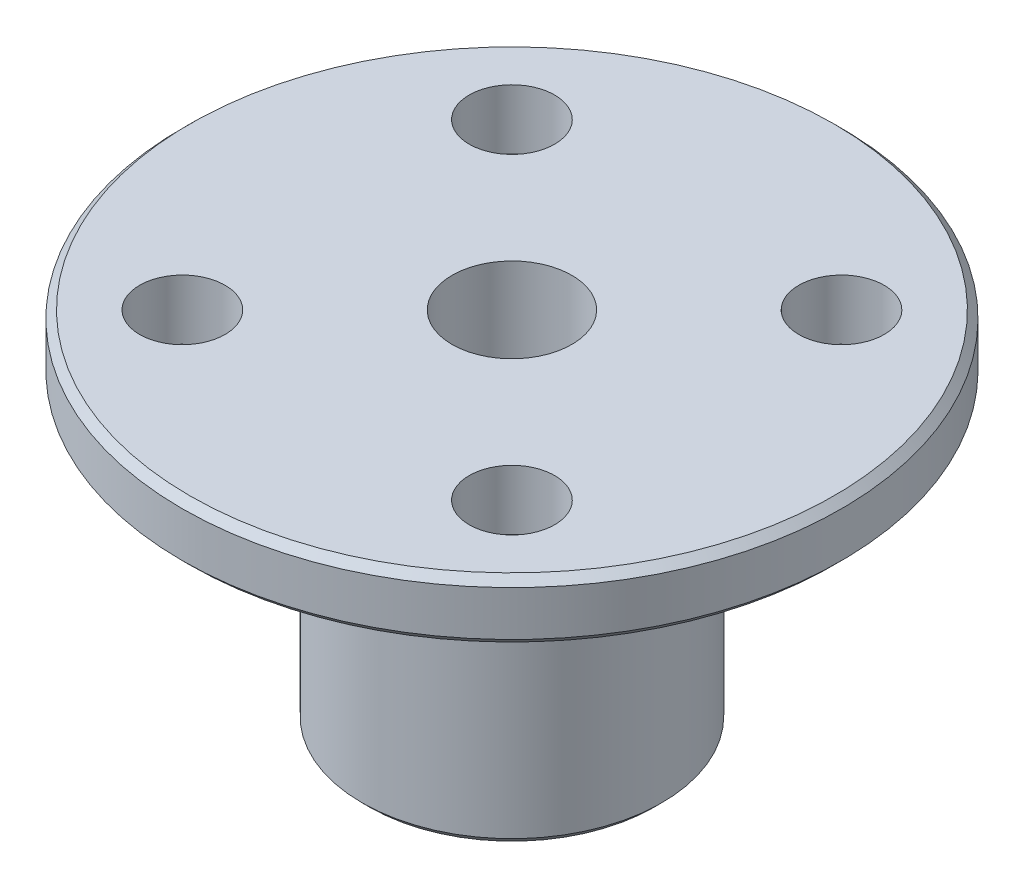
SolidWorks part; units mm, degrees
note: '?' marks a value the reader was unsure of. The reader was unsure of these and kept them because the rebuilt part matched: shared geometry of "Sketch1<3>".
ref_plane "Front Plane" through (0, 0, 0) normal (0, 0, 1) x (1, 0, 0)
ref_plane "Top Plane" through (0, 0, 0) normal (0, 1, 0) x (1, 0, 0)
ref_plane "Right Plane" through (0, 0, 0) normal (1, 0, 0) x (0, 0, -1)
ref_axis "X" through (-88.99, 0, 0) along (1, 0, 0)?
ref_axis "Y" through (0, 55, 0) along (0, -1, 0)?
ref_axis "Z" through (0, 0, -88.99) along (0, 0, 1)?
sketch "Sketch1" plane through (0, 0, 0) normal (0, 1, 0) x (1, 0, 0)
  line L1 (-5.5, 5.5) -> (5.5, 5.5)
  line L2 (-5.5, 5.5) -> (-5.5, -5.5)
  line L3 (-5.5, -5.5) -> (5.5, -5.5)
  line L4 (5.5, 5.5) -> (5.5, -5.5)
  line L5 (-5.5, 5.5) -> (5.5, -5.5) construction
  line L6 (-5.5, -5.5) -> (5.5, 5.5) construction
  circle A0 centre (0, 0) radius 11
  circle A1 centre (0, 0) radius 2
  circle A2 centre (0, 0) radius 5
  circle A3 centre (-5.5, 5.5) radius 1.425
  circle A4 centre (5.5, 5.5) radius 1.425
  circle A5 centre (5.5, -5.5) radius 1.425
  circle A6 centre (-5.5, -5.5) radius 1.425
  dimension "D1" = 22
  dimension "D2" = 4
  dimension "D3" = 10
  dimension "D5" = 2.85
  dimension "D4" = 11
extrude "Boss-Extrude1" add sketch "Sketch1" against normal blind 2 contours A0 A6 L2 A3 L1 A4 L4 A5 L3 | A6 L3 A5 L4 A4 L1 A3 L2 A2 | A2 A1
extrude "Boss-Extrude2" add sketch "Sketch1<3>" against normal blind 12 contours A2 A1
sketch "Sketch1<3>" plane through (0, 0, 0) normal (0, 1, 0) x (1, 0, 0) same geometry as "Sketch1"
chamfer "Chamfer1" distance 0.25 angle 45 5 edges at (0, -12, 2) (0, -2, 5) (0, -12, 5) (0, -2, 11) (0, 0, 11)
